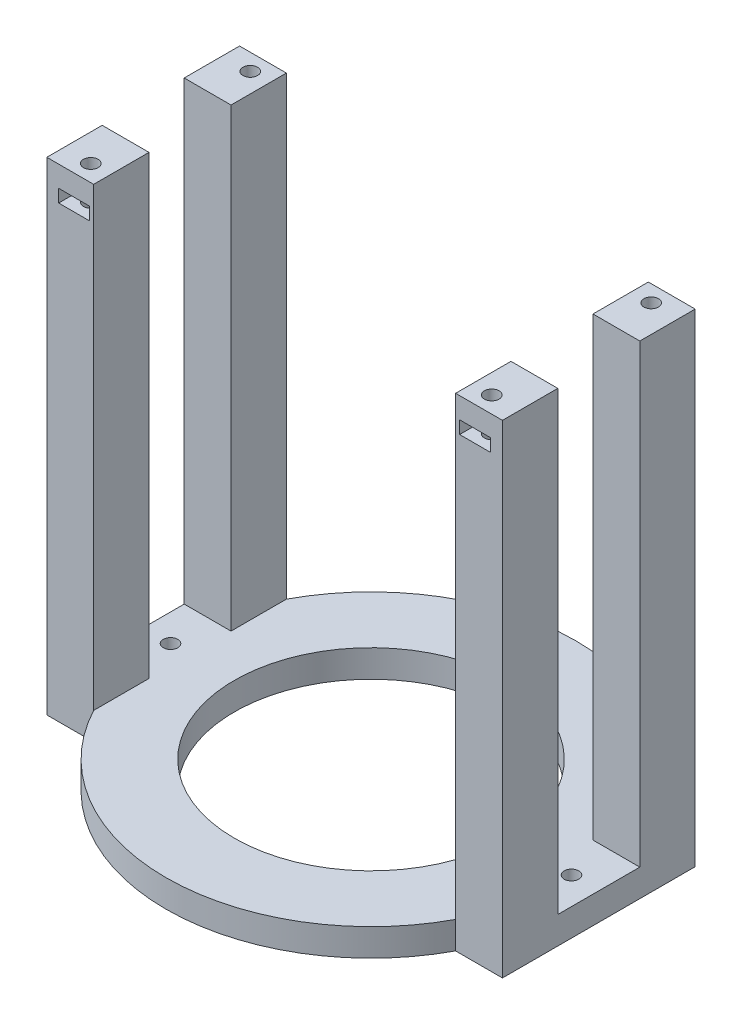
SolidWorks part; units mm, degrees
ref_plane "Front Plane" through (0, 0, 0) normal (0, 0, 1) x (1, 0, 0)
ref_plane "Top Plane" through (0, 0, 0) normal (0, 1, 0) x (1, 0, 0)
ref_plane "Right Plane" through (0, 0, 0) normal (1, 0, 0) x (0, 0, -1)
sketch "Sketch1" plane through (0, 0, 0) normal (0, 1, 0) x (1, 0, 0)
  line L0 (33, 0) -> (-33, 0) construction
  line L2 (-16, 21.15) -> (-50, 21.15)
  line L3 (-16, 21.15) -> (-16, -21.15)
  line L4 (-16, -21.15) -> (-50, -21.15)
  line L5 (-50, 21.15) -> (-50, -21.15)
  line L6 (-16, 21.15) -> (-50, -21.15) construction
  line L7 (-16, -21.15) -> (-50, 21.15) construction
  line L8 (16, 21.15) -> (50, 21.15)
  line L9 (16, 21.15) -> (16, -21.15)
  line L10 (16, -21.15) -> (50, -21.15)
  line L11 (50, 21.15) -> (50, -21.15)
  line L12 (16, 21.15) -> (50, -21.15) construction
  line L13 (16, -21.15) -> (50, 21.15) construction
  circle A0 centre (0, 0) radius 45
  point P6 (0, 0)
  dimension "D1" = 90
  dimension "D2" = 66
  dimension "D3" = 42.3
  dimension "D4" = 42.3
  dimension "D5" = 34
  dimension "D6" = 34
extrude "body" add sketch "Sketch1" along normal blind 6 contours A0 L2 L5 L4 | L2 A0 L4 L3 | L8 A0 L2 L3 L4 L10 L9 | L10 A0 L8 L9 | A0 L10 L11 L8 region at (-29.6863, 0, 0) region at (0, 0, 0) region at (-46.4607, 0, 0) region at (29.6863, 0, 0) region at (46.4607, 0, 0)
sketch "Sketch2" plane through (0, 6, 0) normal (0, 1, 0) x (1, 0, 0)
  line L1 (-50, 21.15) -> (-39.72, 21.15)
  line L2 (-50, 21.15) -> (-50, -21.15)
  line L3 (-50, -21.15) -> (-39.72, -21.15)
  line L4 (-39.72, 21.15) -> (-39.72, -21.15)
  line L5 (50, 21.15) -> (39.72, 21.15)
  line L6 (50, 21.15) -> (50, -21.15)
  line L7 (50, -21.15) -> (39.72, -21.15)
  line L8 (39.72, 21.15) -> (39.72, -21.15)
  line M6 (39.72, -21.15) -> (50, -21.15)
  line M7 (50, -21.15) -> (50, 21.15)
  line M8 (50, 21.15) -> (39.72, 21.15)
extrude "wings" add sketch "Sketch2" along normal blind 100 contours L8 M8 M6 M7 | L2 L1 L4 L3 region at (44.86, 6, 0)
sketch "Sketch3" plane through (0, 106, 0) normal (0, 1, 0) x (1, 0, 0)
  line L0 (44, 0) -> (-44, 0) construction
  line L1 (44, -17.5) -> (44, 17.5) construction
  line L2 (-44, -17.5) -> (-44, 17.5) construction
  circle A0 centre (44, -17.5) radius 1.6
  circle A1 centre (-44, -17.5) radius 1.6
  circle A2 centre (-44, 17.5) radius 1.6
  circle A3 centre (44, 17.5) radius 1.6
  point P4 (0, 0)
  point P8 (44, 0)
  point P11 (-44, 0)
  dimension "D4" = 3.2
  dimension "D5" = 3.2
  dimension "D6" = 3.2
  dimension "D7" = 3.2
  dimension "D1" = 88
  dimension "D2" = 35
  dimension "D3" = 35
extrude "mounting-bore" cut sketch "Sketch3" against normal through all
sketch "Sketch5" plane through (50, 0, 0) normal (1, 0, 0) x (0, 0, -1)
  line L0 (0, 0) -> (0, 6)
  line L1 (21.15, 0) -> (-21.15, 0) construction
  line L2 (9, 6) -> (-9, 6)
  line L3 (9, 6) -> (-9, 6)
  line L4 (9, 6) -> (9, 106)
  line L5 (-9, 6) -> (-9, 106)
  line L6 (9, 106) -> (-9, 106)
  point P7 (0, 6)
  line M9 (21.15, 106) -> (-21.15, 106)
  dimension "D1" = 6
  dimension "D2" = 18
  dimension "D3" = 100
extrude "cut-excess-material" cut sketch "Sketch5" against normal through all contours L5 L2 L4 M9 region at (50, 56, 0)
sketch "Sketch6" plane through (0, 0, 0) normal (0, -1, 0) x (1, 0, 0)
  line L0 (-44, 0) -> (44, 0)
  circle A0 centre (-44, 0) radius 1.6
  circle A1 centre (44, 0) radius 1.6
  point P4 (0, 0)
  dimension "D2" = 3.2
  dimension "D3" = 3.2
  dimension "D1" = 88
extrude "cut-harness-mount" cut sketch "Sketch6" against normal up to next contours A0 | A1 region at (44, 0, 1.5547) region at (-45.5547, 0, 0)
sketch "Sketch8" plane through (0, 0, 21.15) normal (0, 0, 1) x (1, 0, 0)
  line L0 (39.72, 106) -> (44, 106)
  line L1 (39.72, 106) -> (50, 106) construction
  line L2 (44, 106) -> (44, 100)
  line L4 (40.6, 101.4) -> (47.4, 101.4)
  line L5 (40.6, 101.4) -> (40.6, 98.6)
  line L6 (40.6, 98.6) -> (47.4, 98.6)
  line L7 (47.4, 101.4) -> (47.4, 98.6)
  line L8 (40.6, 101.4) -> (47.4, 98.6) construction
  line L9 (40.6, 98.6) -> (47.4, 101.4) construction
  dimension "D1" = 4.28
  dimension "D2" = 6
  dimension "D3" = 6.8
  dimension "D4" = 2.8
extrude "capture-nut-1" cut sketch "Sketch8" against normal blind 7.3 contours L5 L4 L7 L6
pattern_circular "CirPattern1" count 2 over 360 about axis through (0, 6, 0) along (0, 1, 0) of "capture-nut-1"
sketch "Sketch10" plane through (0, 0, -21.15) normal (0, 0, -1) x (-1, 0, 0)
  line L0 (-39.72, 106) -> (-44, 106)
  line L1 (-50, 106) -> (-39.72, 106) construction
  line L2 (-44, 106) -> (-44, 100)
  line L4 (-47.4, 101.4) -> (-40.6, 101.4)
  line L5 (-47.4, 101.4) -> (-47.4, 98.6)
  line L6 (-47.4, 98.6) -> (-40.6, 98.6)
  line L7 (-40.6, 101.4) -> (-40.6, 98.6)
  line L8 (-47.4, 101.4) -> (-40.6, 98.6) construction
  line L9 (-47.4, 98.6) -> (-40.6, 101.4) construction
  dimension "D1" = 4.28
  dimension "D2" = 6
  dimension "D3" = 6.8
  dimension "D4" = 2.8
extrude "capture-nut-2" cut sketch "Sketch10" against normal blind 7.3 contours L7 L4 L5 L6 region at (45.7, 101.3265, -21.15)
pattern_circular "CirPattern2" count 2 over 360 about axis through (0, 6, 0) along (0, 1, 0) of "capture-nut-2"
sketch "Sketch11" plane through (0, 0, 0) normal (0, -1, 0) x (1, 0, 0)
  circle A0 centre (0, 0) radius 30
  dimension "D1" = 60
extrude "Cut-Extrude5" cut sketch "Sketch11" against normal up to next
equation "\"th\"= 6mm"
equation "\"D1@body\"=\"th\""
equation "\"wing\"= 100mm"
equation "\"D1@wings\"=\"wing\""
equation "\"D1@Sketch5\"=\"th\""
equation "\"D3@Sketch5\"=\"wing\""
equation "\"capture_nut_depth\"= 7.3mm"
equation "\"capture_nut_height\"= 2.8mm"
equation "\"capture_nut_width\"= 6.8mm"
equation "\"D3@Sketch8\"=\"capture_nut_width\""
equation "\"D4@Sketch8\"=\"capture_nut_height\""
equation "\"D1@capture-nut-1\" = \"capture_nut_depth\""
equation "\"D3@Sketch10\"=\"capture_nut_width\""
equation "\"D4@Sketch10\"=\"capture_nut_height\""
equation "\"D1@capture-nut-2\" = \"capture_nut_depth\""
